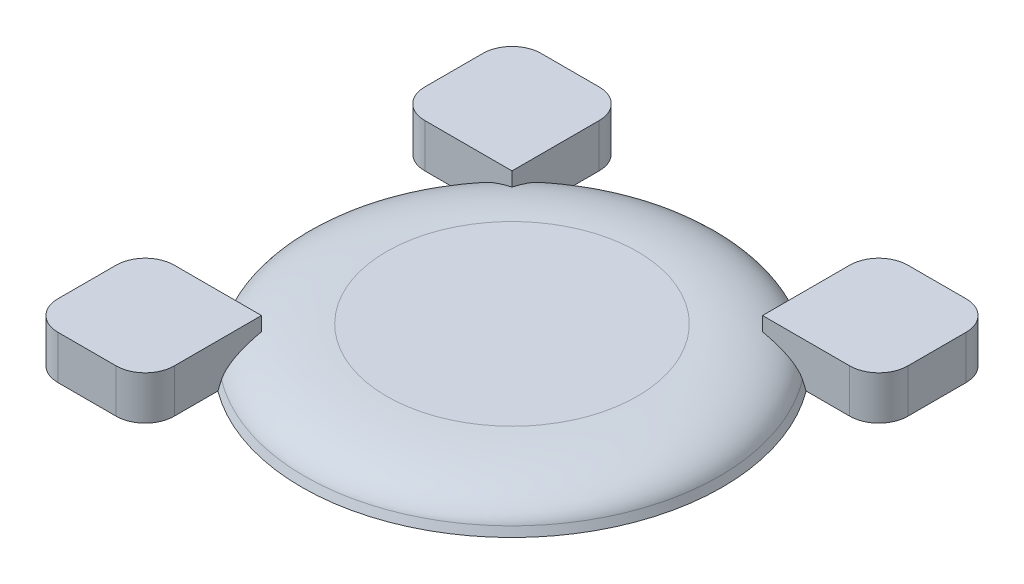
SolidWorks part; units mm, degrees
material "ABS"
ref_plane "Front Plane" through (0, 0, 0) normal (0, 0, 1) x (1, 0, 0)
ref_plane "Top Plane" through (0, 0, 0) normal (0, 1, 0) x (1, 0, 0)
ref_plane "Right Plane" through (0, 0, 0) normal (1, 0, 0) x (0, 0, -1)
sketch "Sketch1" plane through (0, 0, 0) normal (0, 1, 0) x (1, 0, 0)
  line L1 (-17.5, 17.5) -> (17.5, 17.5)
  line L2 (-17.5, 17.5) -> (-17.5, -17.5)
  line L3 (-17.5, -17.5) -> (17.5, -17.5)
  line L4 (17.5, 17.5) -> (17.5, -17.5)
  line L5 (-17.5, 17.5) -> (17.5, -17.5) construction
  line L6 (-17.5, -17.5) -> (17.5, 17.5) construction
  point P0 (0, 0)
  dimension "D1" = 35
sketch "Sketch2" plane through (0, 0, 0) normal (0, 1, 0) x (1, 0, 0)
  circle A0 centre (0, 0) radius 14.4638
extrude "Boss-Extrude1" add sketch "Sketch2" along normal blind 2.5 draft 20
fillet "Fillet1" radius 4 1 edges at (0, 2.5, 13.5539) second distance 6 first distance on face at (0, 2.5, 13.5539)
sketch "Sketch4" plane through (0, 0, 0) normal (0, 1, 0) x (1, 0, 0)
  line L0 (-17.5, -17.5) -> (17.5, 17.5) construction
  line L1 (-16.6164, -16.6164) -> (-8.6164, -16.6164)
  line L2 (-16.6164, -16.6164) -> (-16.6164, -8.6164)
  line L3 (-16.6164, -8.6164) -> (-8.6164, -8.6164)
  line L4 (-8.6164, -16.6164) -> (-8.6164, -8.6164)
  line L5 (-16.6164, -16.6164) -> (-8.6164, -8.6164) construction
  line L6 (-16.6164, -8.6164) -> (-8.6164, -16.6164) construction
  point P0 (-12.6164, -12.6164)
  point P5 (0, 0)
  dimension "D1" = 8
extrude "Boss-Extrude2" add sketch "Sketch4" along normal blind 3
fillet "Fillet2" radius 2 3 edges at (-8.6164, 1.5, 16.6164) (-16.6164, 1.5, 16.6164) (-16.6164, 1.5, 8.6164)
pattern_circular "CirPattern1" count 4 over 360 about axis through (0, 0, 0) along (0, 1, 0) skipping 1 of "Fillet2", "Boss-Extrude2"
